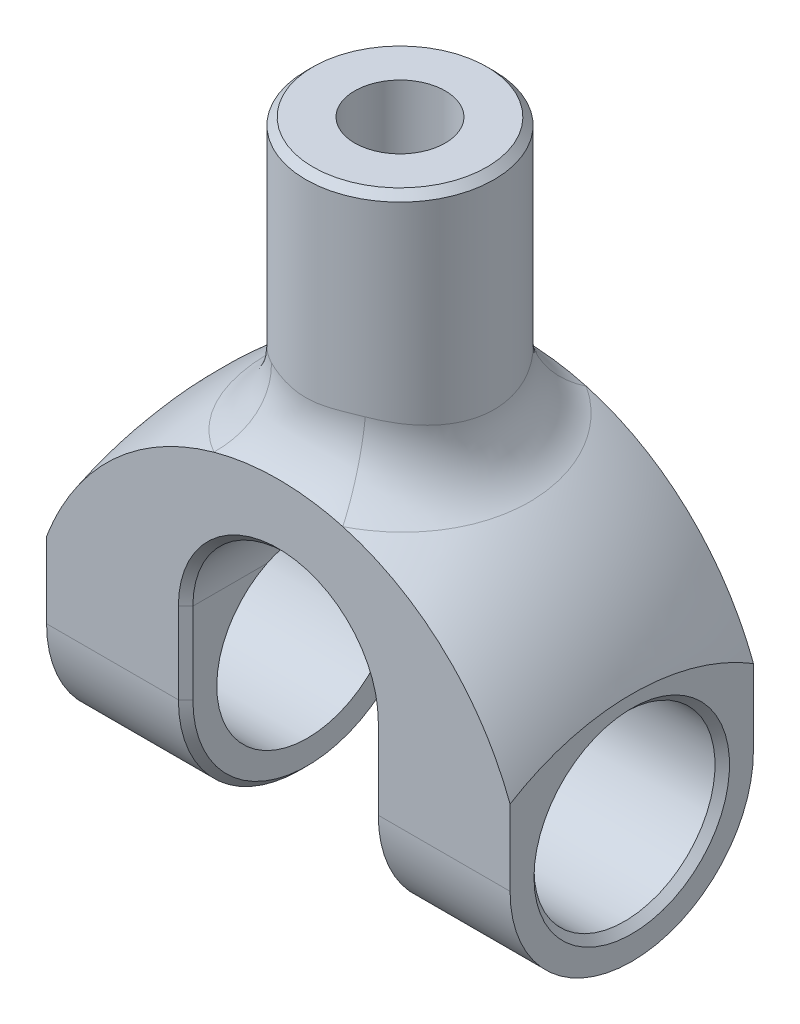
SolidWorks part; units mm, degrees
material "6061-T6 (SS)"
ref_plane "Front" through (0, 0, 0) normal (0, 0, 1) x (1, 0, 0)
ref_plane "Top" through (0, 0, 0) normal (0, 1, 0) x (1, 0, 0)
ref_plane "Right" through (0, 0, 0) normal (1, 0, 0) x (0, 0, -1)
sketch "Sketch1" plane through (0, 0, 0) normal (0, 0, 1) x (1, 0, 0)
  line L0 (-20.32, 0) -> (20.32, 0)
  line L1 (20.32, 0) -> (20.32, 20.32)
  line L2 (20.32, 20.32) -> (-20.32, 20.32) construction
  line L3 (-20.32, 20.32) -> (-20.32, 0)
  arc A0 (20.32, 20.32) -> (-20.32, 20.32) centre (0, 11.3173) ccw
  point P7 (0, 33.5423)
  dimension "D3" = 22.225
  dimension "D1" = 40.64
  dimension "D2" = 20.32
revolve "Revolve1" add sketch "Sketch1" angle 180 mid plane about L0
sketch "Sketch2" plane through (-20.32, 0, 0) normal (-1, 0, 0) x (0, 0, 1)
  line L0 (0, 0) -> (0, 41.4534) construction
  line L1 (-10.668, 10.668) -> (-10.668, 43.8736)
  line L2 (-10.668, 43.8736) -> (-51.2969, 43.8736)
  line L3 (-51.2969, 43.8736) -> (-51.2969, -20.8352)
  line L4 (-51.2969, -20.8352) -> (56.5139, -20.8352)
  line L5 (56.5139, -20.8352) -> (56.5139, 43.8736)
  line L6 (56.5139, 43.8736) -> (10.668, 43.8736)
  line L7 (10.668, 43.8736) -> (10.668, 10.668)
  arc A0 (-10.668, 10.668) -> (10.668, 10.668) centre (0, 10.668) ccw
  circle A1 centre (0, 10.668) radius 7.9375
  dimension "D1" = 10.668
  dimension "D2" = 15.875
extrude "Cut-Extrude1" cut sketch "Sketch2" against normal through all
sketch "Sketch3" plane through (0, 0, -10.668) normal (0, 0, -1) x (-1, 0, 0)
  line L0 (-8.128, 0) -> (8.128, 0)
  line L1 (-20.32, 0) -> (20.32, 0) construction
  line L2 (8.128, 0) -> (8.128, 17.78)
  line L3 (-8.128, 17.78) -> (-8.128, 0)
  line L4 (-20.32, 10.668) -> (-20.32, 0) construction
  arc A0 (8.128, 17.78) -> (-8.128, 17.78) centre (0, 17.78) ccw
  dimension "D1" = 12.192
  dimension "D2" = 17.78
extrude "Cut-Extrude2" cut sketch "Sketch3" against normal through all
ref_plane "Plane1" through (0, 53.975, 0) normal (0, 1, 0) x (-1, 0, 0)
sketch "Sketch4" plane through (0, 53.975, 0) normal (0, 1, 0) x (-1, 0, 0)
  circle A0 centre (0, 0) radius 8.255
  dimension "D1" = 16.51
extrude "Boss-Extrude1" add sketch "Sketch4" against normal up to surface (21.4644 mm away) up to face at (0, -5.601, 0)
sketch "Sketch5" plane through (0, 53.975, 0) normal (0, 1, 0) x (1, 0, 0)
  circle A0 centre (0, 0) radius 3.9688
  dimension "D1" = 7.9375
extrude "Cut-Extrude3" cut sketch "Sketch5" against normal through all
cosmetic thread "Cosmetic Thread2" parameters "D2"=9.525
fillet "Fillet1" radius 6.35 1 edges at (7.0081, 32.1135, 4.3625)
chamfer "Chamfer1" distance 0.635 angle 45 1 edges at (0, 53.975, 8.255)
chamfer "Chamfer2" distance 0.635 angle 45 10 edges at (-20.32, 10.668, 7.9375) (20.32, 10.668, 7.9375) (8.128, 14.224, 10.668) (0, 25.908, 10.668) (-8.128, 14.224, 10.668) (-8.128, 0, 0) (8.128, 0, 0) (-8.128, 14.224, -10.668) (8.128, 14.224, -10.668) (0, 25.908, -10.668)
